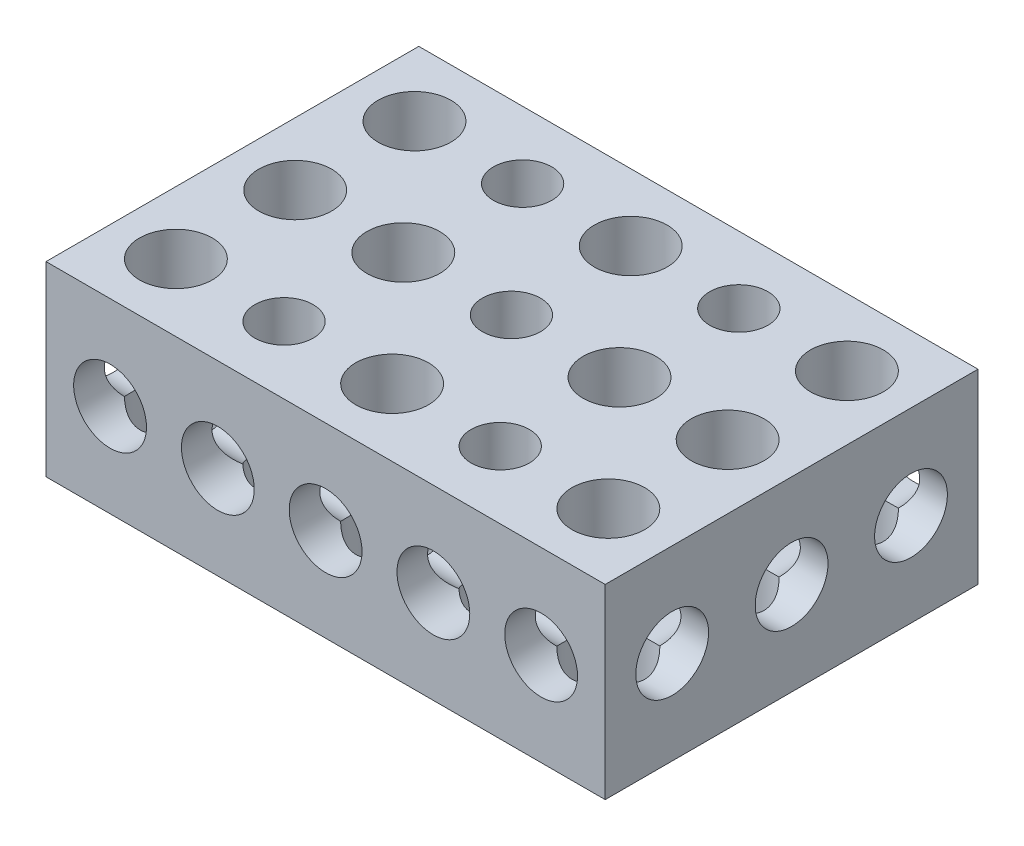
SolidWorks part; units mm, degrees
ref_plane "Front Plane" through (0, 0, 0) normal (0, 0, 1) x (1, 0, 0)
ref_plane "Top Plane" through (0, 0, 0) normal (0, 1, 0) x (1, 0, 0)
ref_plane "Right Plane" through (0, 0, 0) normal (1, 0, 0) x (0, 0, -1)
sketch "Sketch1" plane through (0, 0, 0) normal (0, 0, 1) x (1, 0, 0)
  line L0 (-76.2, 12.7) -> (0, 12.7) construction
  line L1 (0, 0) -> (-76.2, 0)
  line L2 (0, 0) -> (0, 25.4)
  line L3 (0, 25.4) -> (-76.2, 25.4)
  line L4 (-76.2, 0) -> (-76.2, 25.4)
  circle A0 centre (-67.4688, 12.7) radius 4.9609
  circle A1 centre (-52.7844, 12.7) radius 4.9609
  circle A2 centre (-38.1, 12.7) radius 4.9609
  circle A3 centre (-23.4156, 12.7) radius 4.9609
  circle A4 centre (-8.7312, 12.7) radius 4.9609
  dimension "D3" = 9.9219
  dimension "D1" = 76.2
  dimension "D2" = 25.4
  dimension "D4" = 8.7312
  dimension "D6" = 8.7312
  dimension "D5" = 5
extrude "Boss-Extrude1" add sketch "Sketch1" against normal blind 50.8
sketch "Sketch2" plane through (0, 0, 0) normal (1, 0, 0) x (0, 0, -1)
  line L0 (50.8, 12.7) -> (0, 12.7) construction
  line L1 (50.8, 0) -> (50.8, 25.4) construction
  line L2 (0, 0) -> (0, 25.4) construction
  line L3 (25.4, 0) -> (25.4, 25.4) construction
  line L4 (50.8, 0) -> (0, 0) construction
  line L5 (50.8, 25.4) -> (0, 25.4) construction
  circle A0 centre (25.4, 12.7) radius 4.9609
  circle A1 centre (41.6719, 12.7) radius 4.9609
  circle A2 centre (9.1281, 12.7) radius 4.9609
  dimension "D1" = 9.9219
  dimension "D2" = 16.2719
  dimension "D3" = 16.2719
sketch "Sketch3" plane through (0, 25.4, 0) normal (0, 1, 0) x (1, 0, 0)
  line L0 (0, 50.8) -> (0, 0) construction
  line L1 (0, 50.8) -> (-76.2, 50.8) construction
  circle A0 centre (-8.7312, 41.6719) radius 4.9609
  circle A4 centre (-67.6592, 41.6719) radius 4.9609
  circle A8 centre (-67.6592, 25.4159) radius 4.9609
  circle A12 centre (-67.6592, 9.1599) radius 4.9609
  circle A13 centre (-8.7312, 25.4159) radius 4.9609
  circle A14 centre (-8.7312, 9.1599) radius 4.9609
  circle A15 centre (-38.1952, 41.6719) radius 4.9609
  circle A16 centre (-23.4632, 25.4159) radius 4.9609
  circle A17 centre (-52.9272, 25.4159) radius 4.9609
  circle A18 centre (-38.1952, 9.1599) radius 4.9609
  circle A19 centre (-23.4632, 41.6719) radius 4.9609 [skipped]
  circle A20 centre (-52.9272, 41.6719) radius 4.9609 [skipped]
  circle A21 centre (-38.1952, 25.4159) radius 4.9609 [skipped]
  circle A22 centre (-23.4632, 9.1599) radius 4.9609 [skipped]
  circle A23 centre (-52.9272, 9.1599) radius 4.9609 [skipped]
  dimension "D1" = 8.7312
  dimension "D2" = 9.1281
  dimension "D3" = 5
  dimension "D4" = 3
extrude "Cut-Extrude2" cut sketch "Sketch3" against normal through all
sketch "Sketch6" plane through (0, 25.4, 0) normal (0, 1, 0) x (1, 0, 0)
  line L0 (-23.4632, 25.4159) -> (-52.9272, 25.4159) construction
  line L1 (-23.4632, 50.8) -> (-23.4632, 0) construction
  line L2 (0, 0) -> (-76.2, 0) construction
  line L3 (-52.9272, 0) -> (-52.9272, 50.8) construction
  line L4 (0, 50.8) -> (-76.2, 50.8) construction
  line L6 (-23.4632, 41.6719) -> (-52.9272, 41.6719) construction
  line L7 (-23.4632, 9.1599) -> (-52.9272, 9.1599) construction
  circle A0 centre (-52.9272, 9.1599) radius 4.7625
  circle A1 centre (-23.4632, 9.1599) radius 4.7625
  circle A2 centre (-38.1952, 25.4159) radius 4.7625
  circle A3 centre (-23.4632, 41.6719) radius 4.7625
  circle A4 centre (-52.9272, 41.6719) radius 4.7625
hole_wizard "3/8-16 Tapped Hole1" positions "Sketch7" profile "Sketch8" tap size "3/8-16" standard "ANSI Inch" end condition through all
sketch "Sketch7" plane through (0, 25.4, 0) normal (0, 1, 0) x (1, 0, 0)
  point P0 (-23.4632, 41.6719)
  point P3 (-23.4632, 9.1599)
  point P6 (-38.1952, 25.4159)
  point P9 (-52.9272, 41.6719)
  point P12 (-52.9272, 9.1599)
sketch "Sketch8" plane through (-23.4632, 25.4, -41.6719) normal (1, 0, 0) x (0, 0, 1)
  line L0 (0, 0) -> (0, 25.4)
  line L1 (0, 25.4) -> (3.9687, 25.4)
  line L2 (3.9687, 25.4) -> (3.9687, 0)
  line L5 (3.9687, 0) -> (0, 0)
  line L11 (0, -6.35) -> (0, 107.95) construction
  dimension "Thru Tap Drill Dia." = 7.9375
  dimension "Thru Tap Drill Depth" = 25.4
cosmetic thread "Hole Thread1" parameters "D2"=9.525
cosmetic thread "Hole Thread2" parameters "D2"=9.525
cosmetic thread "Hole Thread3" parameters "D2"=9.525
cosmetic thread "Hole Thread4" parameters "D2"=9.525
cosmetic thread "Hole Thread5" parameters "D2"=9.525
extrude "Cut-Extrude4" cut sketch "Sketch2" against normal up to surface (76.2 mm away) up to face at (-76.2, 12.7, -25.4)
